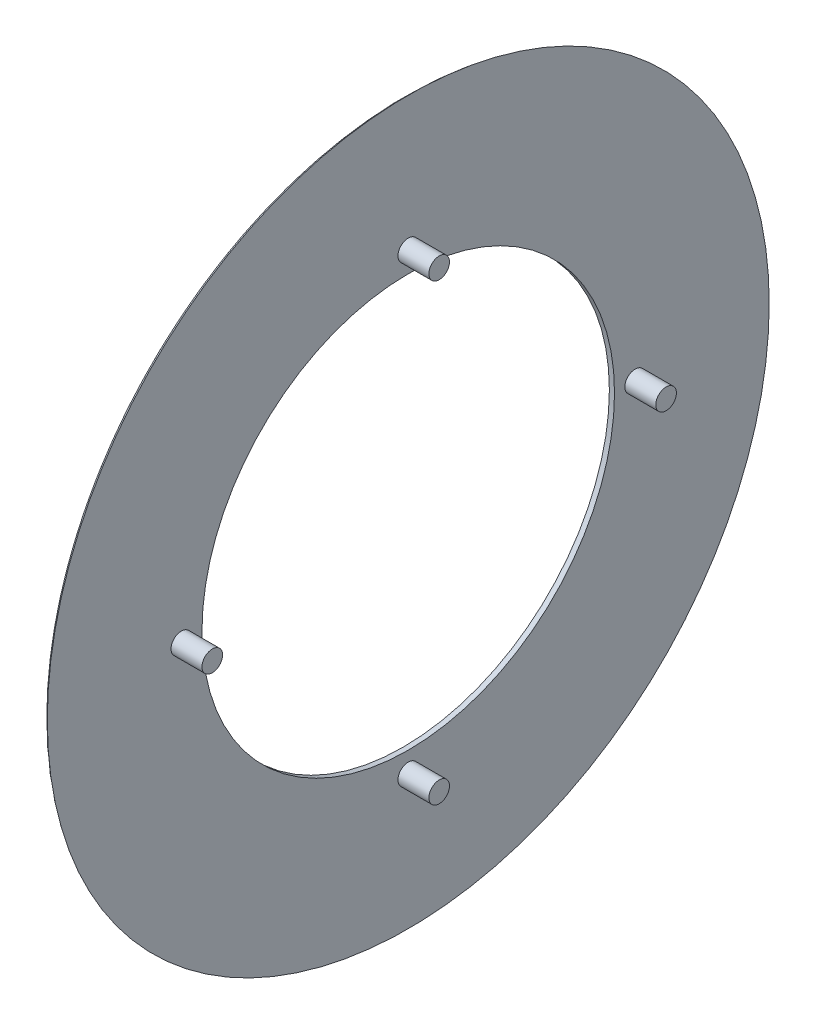
SolidWorks part; units mm, degrees
ref_plane "Front Plane" through (0, 0, 0) normal (0, 0, 1) x (1, 0, 0)
ref_plane "Top Plane" through (0, 0, 0) normal (0, 1, 0) x (1, 0, 0)
ref_plane "Right Plane" through (0, 0, 0) normal (1, 0, 0) x (0, 0, -1)
sketch "Sketch1" plane through (0, 0, 0) normal (1, 0, 0) x (0, 0, -1)
  circle A0 centre (0, 0) radius 44.45
  dimension "D1" = 88.9
extrude "Boss-Extrude1" add sketch "Sketch1" along normal blind 0.635
sketch "Sketch2" plane through (0.635, 0, 0) normal (1, 0, 0) x (0, 0, -1)
  circle A0 centre (0, 0) radius 27.94 construction
  circle A1 centre (0, 27.94) radius 1.27
  circle A2 centre (27.94, 0) radius 1.27
  circle A3 centre (0, -27.94) radius 1.27
  circle A4 centre (-27.94, 0) radius 1.27
  point P14 (0, 0)
  dimension "D1" = 55.88
  dimension "D2" = 2.54
  dimension "D3" = 4
extrude "Boss-Extrude2" add sketch "Sketch2" along normal blind 3.81
sketch "Sketch3" plane through (0.635, 0, 0) normal (1, 0, 0) x (0, 0, -1)
  circle A0 centre (0, 0) radius 25.4
  dimension "D1" = 50.8
extrude "Cut-Extrude1" cut sketch "Sketch3" against normal up to next
fillet "Fillet1" radius 1.27 1 edges at (0, 0, -44.45)
